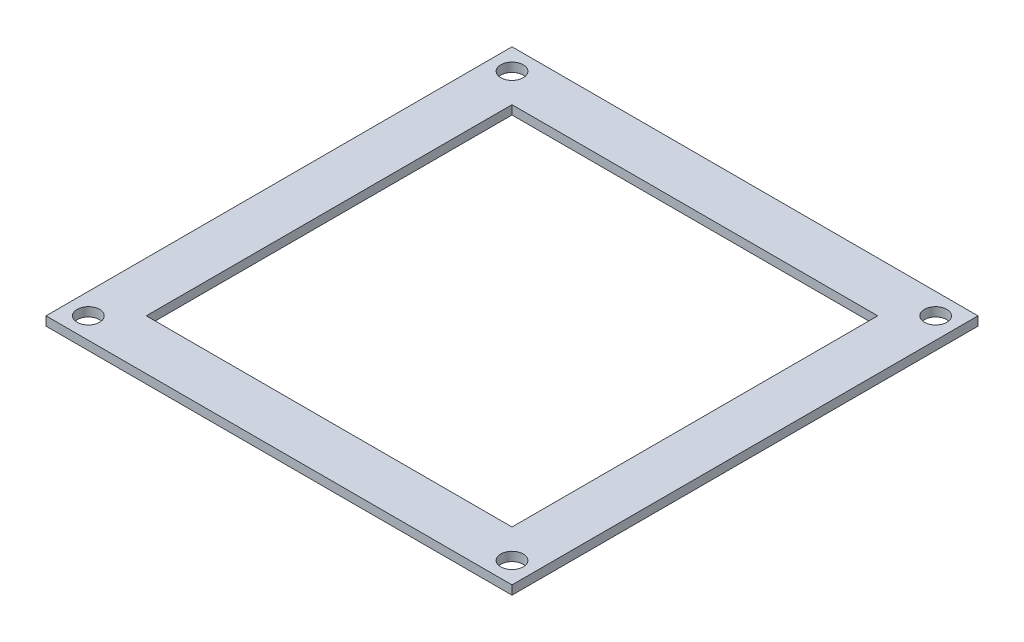
SolidWorks part; units mm, degrees
ref_plane "Front Plane" through (0, 0, 0) normal (0, 0, 1) x (1, 0, 0)
ref_plane "Top Plane" through (0, 0, 0) normal (0, 1, 0) x (1, 0, 0)
ref_plane "Right Plane" through (0, 0, 0) normal (1, 0, 0) x (0, 0, -1)
sketch "Sketch1" plane through (0, 0, 0) normal (0, 1, 0) x (1, 0, 0)
  line L1 (-30, 30) -> (30, 30) construction
  line L2 (-30, 30) -> (-30, -30) construction
  line L3 (-30, -30) -> (30, -30) construction
  line L4 (30, 30) -> (30, -30) construction
  line L5 (0, -30) -> (0, 30) construction
  line L6 (-30, 0) -> (30, 0) construction
  line L7 (-25.9, 25.9) -> (25.9, 25.9)
  line L8 (-25.9, 25.9) -> (-25.9, -25.9)
  line L9 (-25.9, -25.9) -> (25.9, -25.9)
  line L10 (25.9, 25.9) -> (25.9, -25.9)
  line L11 (0, -25.9) -> (0, 25.9) construction
  line L12 (-25.9, 0) -> (25.9, 0) construction
  line L13 (-33, 33) -> (33, 33)
  line L14 (-33, 33) -> (-33, -33)
  line L15 (-33, -33) -> (33, -33)
  line L16 (33, 33) -> (33, -33)
  line L17 (0, -33) -> (0, 33) construction
  line L18 (-33, 0) -> (33, 0) construction
  circle A0 centre (-30, 30) radius 1.59
  circle A1 centre (30, 30) radius 1.59
  circle A2 centre (30, -30) radius 1.59
  circle A3 centre (-30, -30) radius 1.59
  point P0 (0, 0)
  point P9 (0, 0)
  point P13 (0, 0)
  dimension "D1" = 3.18
  dimension "D2" = 60
  dimension "D3" = 51.8
  dimension "D4" = 3
  dimension "D5" = 3
  dimension "D6" = 66
extrude "Boss-Extrude1" add sketch "Sketch1" along normal blind 1.27
equation "\"Lens_dim\"= 50.8"
equation "\"D3@Sketch1\"=\"Lens_dim\" +0.5*2"
equation "\"D5@Sketch1\"=\"D4@Sketch1\""
